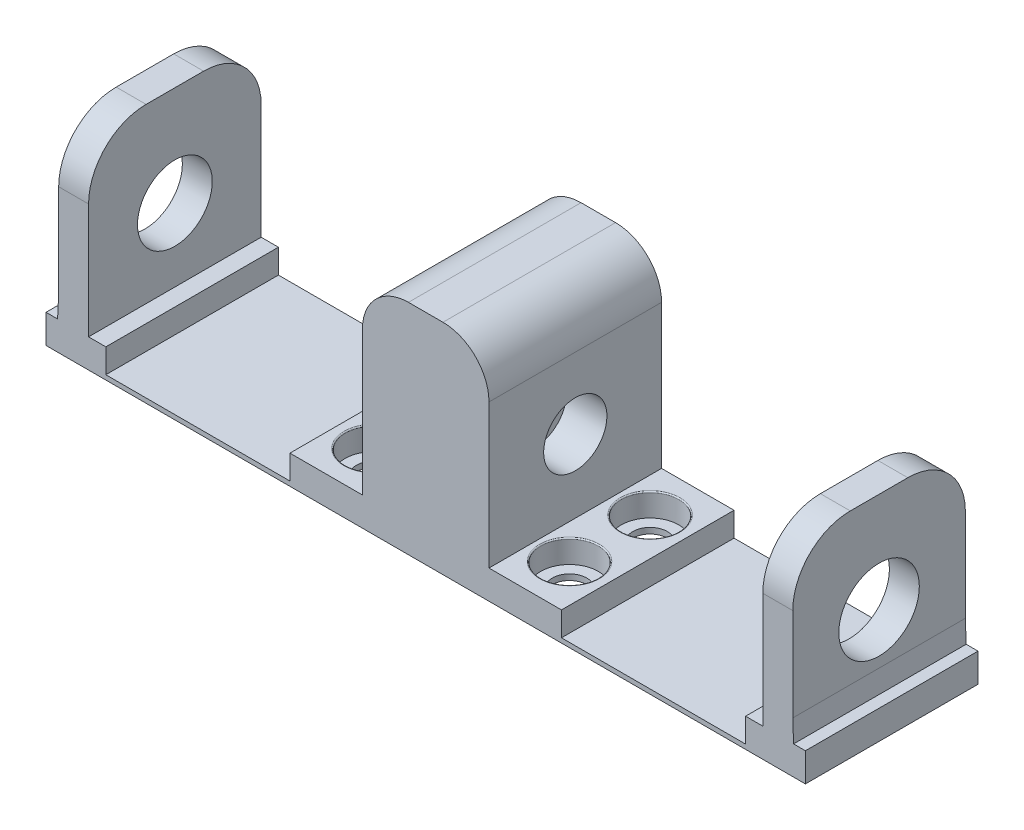
SolidWorks part; units mm, degrees
ref_plane "Alzado" through (0, 0, 0) normal (0, 0, 1) x (1, 0, 0)
ref_plane "Planta" through (0, 0, 0) normal (0, 1, 0) x (1, 0, 0)
ref_plane "Vista lateral" through (0, 0, 0) normal (1, 0, 0) x (0, 0, -1)
sketch "Croquis1" plane through (0, 0, 0) normal (0, 0, 1) x (1, 0, 0)
  line L0 (0, 9.5) -> (0, -9.5) construction
  line L1 (-1.5, 9.5) -> (1.5, 9.5)
  line L2 (-5.5, 5.5) -> (-5.5, -7)
  line L3 (-5.5, -9.5) -> (5.5, -9.5)
  line L4 (5.5, 5.5) -> (5.5, -7)
  line L5 (-5.5, 9.5) -> (5.5, -9.5) construction
  line L6 (-5.5, -9.5) -> (5.5, 9.5) construction
  line L7 (-5.5, -9.5) -> (-11.5, -9.5)
  line L9 (-5.5, -7) -> (-11.5, -7)
  line L10 (-11.5, -9.5) -> (-11.5, -7)
  line L11 (5.5, -7) -> (11.5, -7)
  line L12 (11.5, -9.5) -> (11.5, -7)
  line L13 (5.5, -9.5) -> (11.5, -9.5)
  arc A0 (5.5, 5.5) -> (1.5, 9.5) centre (1.5, 5.5) ccw
  arc A1 (-5.5, 5.5) -> (-1.5, 9.5) centre (-1.5, 5.5) cw
  point P0 (0, 0)
  dimension "D1" = 4
  dimension "D2" = 6
  dimension "D3" = 2.5
  dimension "D4" = 11
  dimension "D5" = 15
extrude "Saliente-Extruir1" add sketch "Croquis1" against normal blind 15
sketch "Croquis2" plane through (5.5, 0, 0) normal (1, 0, 0) x (0, 0, -1)
  line L0 (7.5, 9.5) -> (7.5, -7) construction
  line L1 (15, 9.5) -> (0, 9.5) construction
  line L2 (15, -7) -> (0, -7) construction
  line L3 (15, -9.5) -> (0, -9.5) construction
  circle A0 centre (7.5, -0.68) radius 2.75
  dimension "D2" = 5.5
  dimension "D1" = 8.82
extrude "Cortar-Extruir1" cut sketch "Croquis2" against normal blind 3.5
sketch "Croquis3" plane through (-5.5, 0, 0) normal (-1, 0, 0) x (0, 0, 1)
  line L0 (-7.5, 9.5) -> (-7.5, -7) construction
  line L1 (-15, 9.5) -> (0, 9.5) construction
  line L2 (-15, -7) -> (0, -7) construction
  line L3 (-15, -9.5) -> (0, -9.5) construction
  circle A0 centre (-7.5, -0.68) radius 2.75
  dimension "D2" = 5.5
  dimension "D1" = 8.82
extrude "Cortar-Extruir2" cut sketch "Croquis3" against normal blind 3.5
sketch "Croquis4" plane through (0, -7, 0) normal (0, 1, 0) x (1, 0, 0)
  line L0 (0, 15) -> (0, 0) construction
  line L1 (1.5, 15) -> (-1.5, 15) construction
  line L2 (-8.5, 15) -> (-8.5, 0) construction
  line L3 (-5.5, 15) -> (-11.5, 15) construction
  line L4 (-5.5, 0) -> (-11.5, 0) construction
  circle A0 centre (-8.5, 11) radius 2.5
  circle A1 centre (-8.5, 4) radius 2.5
  circle A2 centre (8.5, 4) radius 2.5
  circle A3 centre (8.5, 11) radius 2.5
  dimension "D1" = 5
  dimension "D2" = 4
  dimension "D3" = 4
extrude "Cortar-Extruir3" cut sketch "Croquis4" against normal blind 2
fillet "Redondeo1" radius 0.1 4 edges at (11, -7, -4) (11, -7, -11) (-11, -7, -4) (-11, -7, -11)
sketch "Croquis5" plane through (0, -7, 0) normal (0, 1, 0) x (1, 0, 0)
  line L0 (-8.5, 15) -> (-8.5, 0) construction
  line L1 (-5.5, 15) -> (-11.5, 15) construction
  line L2 (-5.5, 0) -> (-11.5, 0) construction
  line L3 (0, 15) -> (0, 0) construction
  line L4 (1.5, 15) -> (-1.5, 15) construction
  line L5 (1.5, 0) -> (-1.5, 0) construction
  circle A0 centre (-8.5, 11) radius 1.5
  circle A1 centre (-8.5, 4) radius 1.5
  circle A2 centre (-8.5, 11) radius 2.6 construction
  circle A3 centre (8.5, 4) radius 1.5
  circle A4 centre (8.5, 11) radius 1.5
  dimension "D1" = 3
extrude "Cortar-Extruir4" cut sketch "Croquis5" against normal through all
sketch "Croquis6" plane through (-11.5, 0, 0) normal (-1, 0, 0) x (0, 0, 1)
  line L1 (-15, -7) -> (0, -7)
  line L2 (-15, -7) -> (-15, -9.5)
  line L3 (-15, -9.5) -> (0, -9.5)
  line L4 (0, -7) -> (0, -9.5)
extrude "Saliente-Extruir2" add sketch "Croquis6" along normal blind 21.5
sketch "Croquis7" plane through (11.5, 0, 0) normal (1, 0, 0) x (0, 0, -1)
  line L1 (0, -7) -> (15, -7)
  line L2 (0, -7) -> (0, -9.5)
  line L3 (0, -9.5) -> (15, -9.5)
  line L4 (15, -7) -> (15, -9.5)
extrude "Saliente-Extruir3" add sketch "Croquis7" along normal blind 21.5
sketch "Croquis8" plane through (0, -7, 0) normal (0, 1, 0) x (1, 0, 0)
  line L0 (-5.5, 15) -> (-33, 15) construction
  line L1 (-31.9, 15) -> (-29.3, 15)
  line L2 (-31.9, 15) -> (-31.9, 0)
  line L3 (-31.9, 0) -> (-29.3, 0)
  line L4 (-29.3, 15) -> (-29.3, 0)
  line L5 (-5.5, 0) -> (-33, 0) construction
  line L6 (0, 15) -> (0, 0) construction
  line L7 (1.5, 15) -> (-1.5, 15) construction
  line L8 (31.9, 0) -> (29.3, 0)
  line L9 (29.3, 15) -> (29.3, 0)
  line L10 (31.9, 15) -> (29.3, 15)
  line L11 (31.9, 15) -> (31.9, 0)
  line L12 (-33, 0) -> (-33, 15) construction
  dimension "D1" = 2.6
  dimension "D2" = 1.1
extrude "Saliente-Extruir4" add sketch "Croquis8" along normal blind 15
fillet "Redondeo4" radius 5 2 edges at (-30.6, 8, -15) (-30.6, 8, 0)
fillet "Redondeo5" radius 5 2 edges at (30.6, 8, -15) (30.6, 8, 0)
ref_plane "Plano12" through (0, 0, -7.5) normal (0, 0, 1) x (1, 0, 0)
sketch "Croquis17" plane through (0, 0, -7.5) normal (0, 0, 1) x (1, 0, 0)
  line L0 (31.9, -5.0818) -> (31.9724, -7)
  line L1 (31.9, 3) -> (31.9, -7) construction
  line L3 (33, -7) -> (31.9, -7) construction
rib "Nervio1" sketch "Croquis17" sketch "Croquis17" thickness 15 extrusion direction parallel to sketch draft on no parameters "D1"=15
sketch "Croquis22" plane through (0, 0, -7.5) normal (0, 0, 1) x (1, 0, 0)
  line L0 (-31.9933, -7) -> (-31.9, -5.0818)
  line L1 (-31.9, -7) -> (-33, -7) construction
  line L2 (-31.9, 8) -> (-31.9, 3) construction
  line L4 (-31.9, 3) -> (-31.9, -7) construction
rib "Nervio2" sketch "Croquis22" sketch "Croquis22" thickness 15 extrusion direction parallel to sketch draft on no parameters "D1"=15
sketch "Croquis23" plane through (31.9, 0, 0) normal (1, 0, 0) x (0, 0, -1)
  line L0 (7.5, 8) -> (7.5, -5.0818) construction
  line L1 (5, 8) -> (10, 8) construction
  line L2 (0, -5.0818) -> (15, -5.0818) construction
  line L3 (0, -9.5) -> (15, -9.5) construction
  circle A0 centre (7.5, -0.68) radius 3.5
  dimension "D1" = 7
  dimension "D2" = 8.82
extrude "Cortar-Extruir5" cut sketch "Croquis23" against normal blind 7
sketch "Croquis24" plane through (-31.9, 0, 0) normal (-1, 0, 0) x (0, 0, 1)
  line L0 (-7.5, 8) -> (-7.5, -5.0818) construction
  line L1 (-10, 8) -> (-5, 8) construction
  line L2 (-15, -5.0818) -> (0, -5.0818) construction
  line L3 (-15, -9.5) -> (0, -9.5) construction
  circle A0 centre (-7.5, -0.68) radius 3.25
  dimension "D1" = 6.5
  dimension "D2" = 8.82
extrude "Cortar-Extruir6" cut sketch "Croquis24" against normal blind 7
sketch "Croquis34" plane through (0, 0, 0) normal (0, 0, 1) x (1, 0, 0)
  line L0 (-29.3, -7) -> (-27.8, -7)
  line L1 (-5.5, -7) -> (-29.3, -7) construction
  line L2 (-27.8, -7) -> (-27.8, -9.1)
  line L3 (-27.8, -9.1) -> (-11.8, -9.1)
  line L4 (-11.8, -9.1) -> (-11.8, -7)
  line L5 (-27.8, -7) -> (-11.8, -7)
  line L6 (0, -9.5) -> (0, 0) construction
  line L8 (27.8, -7) -> (27.8, -9.1)
  line L9 (27.8, -9.1) -> (11.8, -9.1)
  line L10 (11.8, -9.1) -> (11.8, -7)
  line L11 (27.8, -7) -> (11.8, -7)
  line M23 (-5.5, -7) -> (-29.3, -7)
  dimension "D1" = 16
  dimension "D2" = 1.5
  dimension "D3" = 2.1
extrude "Cortar-Extruir7" cut sketch "Croquis34" against normal through all contours L3 L4 L2 M23 | L11 L10 L9 L8 region at (-19.8, -8.05, 0)
sketch "Croquis35" plane through (0, -9.5, 0) normal (0, -1, 0) x (1, 0, 0)
  line L0 (-31, 0) -> (-31, -15) construction
  line L1 (-33, 0) -> (33, 0) construction
  line L2 (-33, -15) -> (33, -15) construction
  line L3 (-33, -15) -> (-33, 0) construction
  line L4 (0, 0) -> (0, -15) construction
  circle A0 centre (-31, -4) radius 1.5
  circle A1 centre (-31, -11) radius 1.5
  circle A2 centre (31, -11) radius 1.5
  circle A3 centre (31, -4) radius 1.5
  dimension "D2" = 3
  dimension "D3" = 4
  dimension "D1" = 2
  dimension "D4" = 4
extrude "Cortar-Extruir8" cut sketch "Croquis35" against normal blind 2.2
